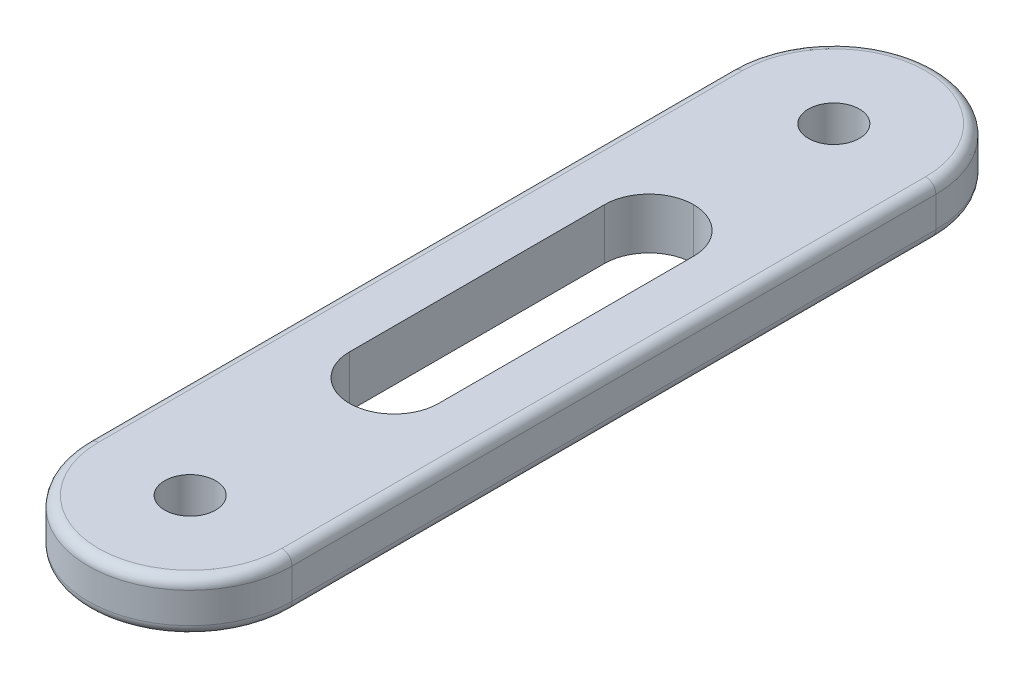
SolidWorks part; units mm, degrees
material "Cast Alloy Steel"
ref_plane "Front Plane" through (0, 0, 0) normal (0, 0, 1) x (1, 0, 0)
ref_plane "Top Plane" through (0, 0, 0) normal (0, 1, 0) x (1, 0, 0)
ref_plane "Right Plane" through (0, 0, 0) normal (1, 0, 0) x (0, 0, -1)
sketch "Sketch1" plane through (0, 0, 0) normal (0, 1, 0) x (1, 0, 0)
  line L0 (12.7, 105.5688) -> (12.7, 0) construction
  line L1 (0, 0) -> (25.4, 0)
  line L2 (0, 0) -> (0, 105.5688)
  line L3 (0, 105.5688) -> (25.4, 105.5688)
  line L4 (25.4, 0) -> (25.4, 105.5688)
  line L5 (7.1437, 75.4063) -> (18.2562, 75.4063)
  line L6 (7.1437, 75.4063) -> (7.1437, 32.5438)
  line L7 (7.1437, 32.5438) -> (18.2563, 32.5438)
  line L8 (18.2562, 75.4063) -> (18.2563, 32.5438)
  circle A0 centre (12.7, 92.8688) radius 3.175
  circle A1 centre (12.7, 12.7) radius 3.175
  point P11 (12.7, 75.4063)
  dimension "D1" = 6.35
  dimension "D2" = 12.7
  dimension "D3" = 25.4
  dimension "D4" = 17.4625
  dimension "D5" = 12.7
  dimension "D6" = 19.8438
  dimension "D7" = 42.8625
  dimension "D8" = 11.1125
extrude "Boss-Extrude1" add sketch "Sketch1" along normal blind 6.35
sketch "Sketch2" plane through (0, 6.35, 0) normal (0, 1, 0) x (1, 0, 0)
  line L0 (0, 0) -> (25.4, 0) construction
  line L1 (25.4, 105.5688) -> (0, 105.5688) construction
  circle A0 centre (12.7, 92.8688) radius 12.7
  circle A1 centre (12.7, 12.7) radius 12.7
  line M3 (25.4, 105.5688) -> (0, 105.5688)
  line M5 (0, 0) -> (25.4, 0)
  line M13 (0, 105.5688) -> (0, 0)
  line M14 (25.4, 0) -> (25.4, 105.5688)
extrude "Cut-Extrude1" cut sketch "Sketch2" against normal through all contours A0 M3 M13 | A0 M14 M3 | A1 M13 M5 | A1 M5 M14 region at (22.5632, 6.35, -102.732) region at (2.8368, 6.35, -102.732) region at (22.5632, 6.35, -2.8368) region at (2.8368, 6.35, -2.8368)
fillet "Fillet1" radius 1.27 8 edges at (0, 6.35, -52.7844) (0, 0, -52.7844) (25.4, 0, -52.7844) (25.4, 6.35, -52.7844) (12.7, 0, 0) (12.7, 0, -105.5688) (12.7, 6.35, 0) (12.7, 6.35, -105.5688)
fillet "Fillet2" radius 5.5562 4 edges at (7.1437, 3.175, -32.5438) (18.2563, 3.175, -32.5438) (18.2562, 3.175, -75.4063) (7.1437, 3.175, -75.4063)
